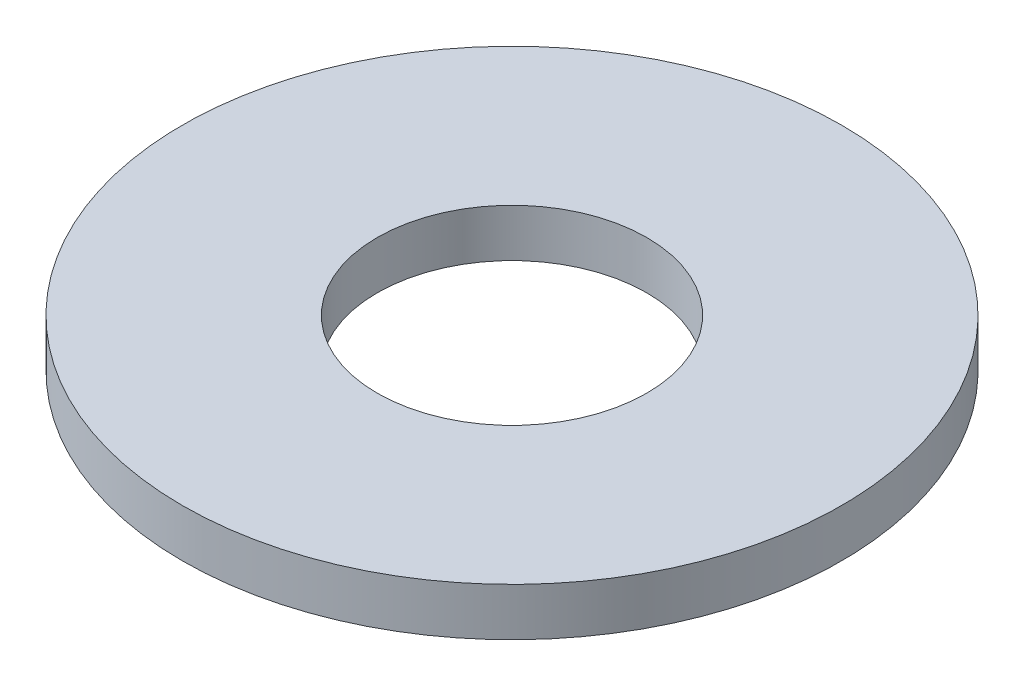
SolidWorks part; units mm, degrees
ref_plane "Front Plane" through (0, 0, 0) normal (0, 0, 1) x (1, 0, 0)
ref_plane "Top Plane" through (0, 0, 0) normal (0, 1, 0) x (1, 0, 0)
ref_plane "Right Plane" through (0, 0, 0) normal (1, 0, 0) x (0, 0, -1)
sketch "Sketch1" plane through (0, 0, 0) normal (0, 1, 0) x (1, 0, 0)
  circle A0 centre (0, 0) radius 55
  dimension "FLANGE_OD" = 110
extrude "Boss-Extrude1" add sketch "Sketch1" along normal blind 8
sketch "Sketch2" plane through (0, 0, 0) normal (0, 1, 0) x (1, 0, 0)
  circle A0 centre (0, 0) radius 22.5
  dimension "BORE_D" = 45
extrude "Cut-Extrude1" cut sketch "Sketch2" along normal through all
sketch "Sketch3" plane through (0, 8, 0) normal (0, 1, 0) x (1, 0, 0)
  circle A0 centre (0, 0) radius 14.4085 construction
  circle A1 centre (-14.4085, 0) radius 5.3019
  dimension "BOLT_D" = 10.6038
  dimension "BOLT_PCD" = 28.817
extrude "Cut-Extrude2" cut sketch "Sketch3" against normal blind 6.1946 rebuild error yes
pattern_circular "CirPattern1" count 3 over 360 rebuild error yes
